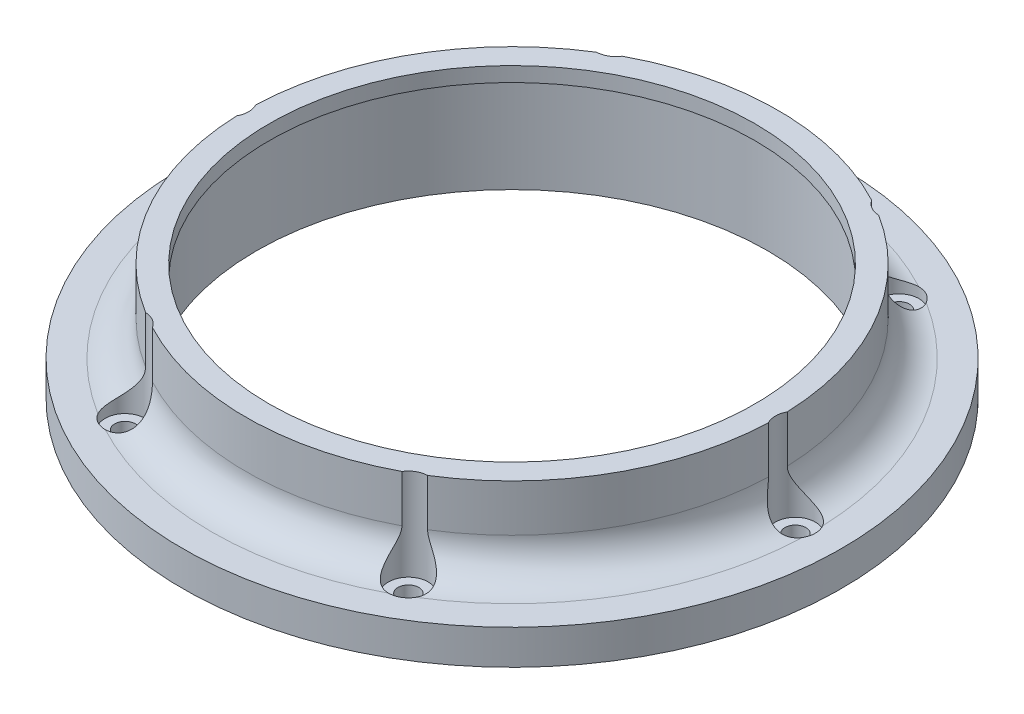
SolidWorks part; units mm, degrees
ref_plane "Front Plane" through (0, 0, 0) normal (0, 0, 1) x (1, 0, 0)
ref_plane "Top Plane" through (0, 0, 0) normal (0, 1, 0) x (1, 0, 0)
ref_plane "Right Plane" through (0, 0, 0) normal (1, 0, 0) x (0, 0, -1)
sketch "Sketch1" plane through (0, 0, 0) normal (0, 1, 0) x (1, 0, 0)
  circle A0 centre (0, 0) radius 61.25 construction
  circle A1 centre (0, 0) radius 55.25
  circle A2 centre (0, 0) radius 57.5
  dimension "D1" = 122.5
  dimension "D2" = 110.5
  dimension "D3" = 115
extrude "Boss-Extrude1" add sketch "Sketch1" along normal blind 22
sketch "Sketch2" plane through (0, 0, 0) normal (0, -1, 0) x (1, 0, 0)
  circle A0 centre (0, 0) radius 61.25 construction
  circle A1 centre (0, 0) radius 71.25
  circle A2 centre (0, 0) radius 57.5 construction
  circle A3 centre (0, 0) radius 57.5
  dimension "D1" = 122.5
  dimension "D2" = 10
extrude "Boss-Extrude2" add sketch "Sketch2" against normal blind 7.5
sketch "Sketch6" plane through (0, 7.5, 0) normal (0, 1, 0) x (1, 0, 0)
  circle A0 centre (0, 0) radius 61.25 construction
  point P0 (-61.25, 0)
  point P7 (0, 0)
  dimension "D1" = 122.5
hole_wizard "CBORE for M4 SBHCS1" positions "Sketch6" profile "Sketch5" counterbore size "M4" standard "ANSI Metric" end condition through all
sketch "Sketch5" plane through (-61.25, 7.5, 0) normal (1, 0, 0) x (0, 0, 1)
  line L0 (0, 0) -> (0, 7.5)
  line L1 (0, 7.5) -> (2.25, 7.5)
  line L3 (2.25, 7.5) -> (2.25, 2.2)
  line L4 (2.25, 2.2) -> (4.3, 2.2)
  line L5 (4.3, 2.2) -> (4.3, 0)
  line L7 (4.3, 0) -> (0, 0)
  line L11 (0, -6.35) -> (0, 107.95) construction
  dimension "Thru Hole Dia." = 4.5
  dimension "Thru Hole Depth" = 7.5
  dimension "C'Bore Dia." = 8.6
  dimension "C'Bore Depth" = 2.2
fillet "Fillet2" radius 7.5 1 edges at (57.5, 7.5, 0)
sketch "Sketch7" plane through (0, 7.5, 0) normal (0, 1, 0) x (1, 0, 0)
  circle A1 centre (-61.25, 0) radius 4.3
  circle A2 centre (-61.25, 0) radius 4.3
  dimension "D1" = 0
extrude "Cut-Extrude1" cut sketch "Sketch7" along normal through all
pattern_circular "CirPattern1" count 6 over 360 about axis through (0, 7.5, 0) along (0, -1, 0) of "Cut-Extrude1", "CBORE for M4 SBHCS1"
sketch "Sketch8" plane through (0, 22, 0) normal (0, 1, 0) x (1, 0, 0)
  circle A0 centre (0, 0) radius 52.5
  arc A12 (-57.4639, -2.0384) -> (-30.4972, -48.746) centre (0, 0) ccw
  arc A13 (-26.9666, -50.7844) -> (-30.4972, -48.746) centre (-30.625, -53.0441) ccw
  arc A14 (-26.9666, -50.7844) -> (26.9666, -50.7844) centre (0, 0) ccw
  arc A15 (30.4972, -48.746) -> (26.9666, -50.7844) centre (30.625, -53.0441) ccw
  arc A16 (30.4972, -48.746) -> (57.4639, -2.0384) centre (0, 0) ccw
  arc A17 (57.4639, 2.0384) -> (57.4639, -2.0384) centre (61.25, 0) ccw
  arc A18 (57.4639, 2.0384) -> (30.4972, 48.746) centre (0, 0) ccw
  arc A19 (26.9666, 50.7844) -> (30.4972, 48.746) centre (30.625, 53.0441) ccw
  arc A20 (26.9666, 50.7844) -> (-26.9666, 50.7844) centre (0, 0) ccw
  arc A21 (-30.4972, 48.746) -> (-26.9666, 50.7844) centre (-30.625, 53.0441) ccw
  arc A22 (-30.4972, 48.746) -> (-57.4639, 2.0384) centre (0, 0) ccw
  arc A23 (-57.4639, -2.0384) -> (-57.4639, 2.0384) centre (-61.25, 0) ccw
  arc A24 (-57.4639, -2.0384) -> (-30.4972, -48.746) centre (0, 0) ccw
  arc A25 (-26.9666, -50.7844) -> (-30.4972, -48.746) centre (-30.625, -53.0441) ccw
  arc A26 (-26.9666, -50.7844) -> (26.9666, -50.7844) centre (0, 0) ccw
  arc A27 (30.4972, -48.746) -> (26.9666, -50.7844) centre (30.625, -53.0441) ccw
  arc A28 (30.4972, -48.746) -> (57.4639, -2.0384) centre (0, 0) ccw
  arc A29 (57.4639, 2.0384) -> (57.4639, -2.0384) centre (61.25, 0) ccw
  arc A30 (57.4639, 2.0384) -> (30.4972, 48.746) centre (0, 0) ccw
  arc A31 (26.9666, 50.7844) -> (30.4972, 48.746) centre (30.625, 53.0441) ccw
  arc A32 (26.9666, 50.7844) -> (-26.9666, 50.7844) centre (0, 0) ccw
  arc A33 (-30.4972, 48.746) -> (-26.9666, 50.7844) centre (-30.625, 53.0441) ccw
  arc A34 (-30.4972, 48.746) -> (-57.4639, 2.0384) centre (0, 0) ccw
  arc A35 (-57.4639, -2.0384) -> (-57.4639, 2.0384) centre (-61.25, 0) ccw
  dimension "D2" = 5
  dimension "D1" = 0
extrude "Boss-Extrude3" add sketch "Sketch8" along normal blind 3.175
